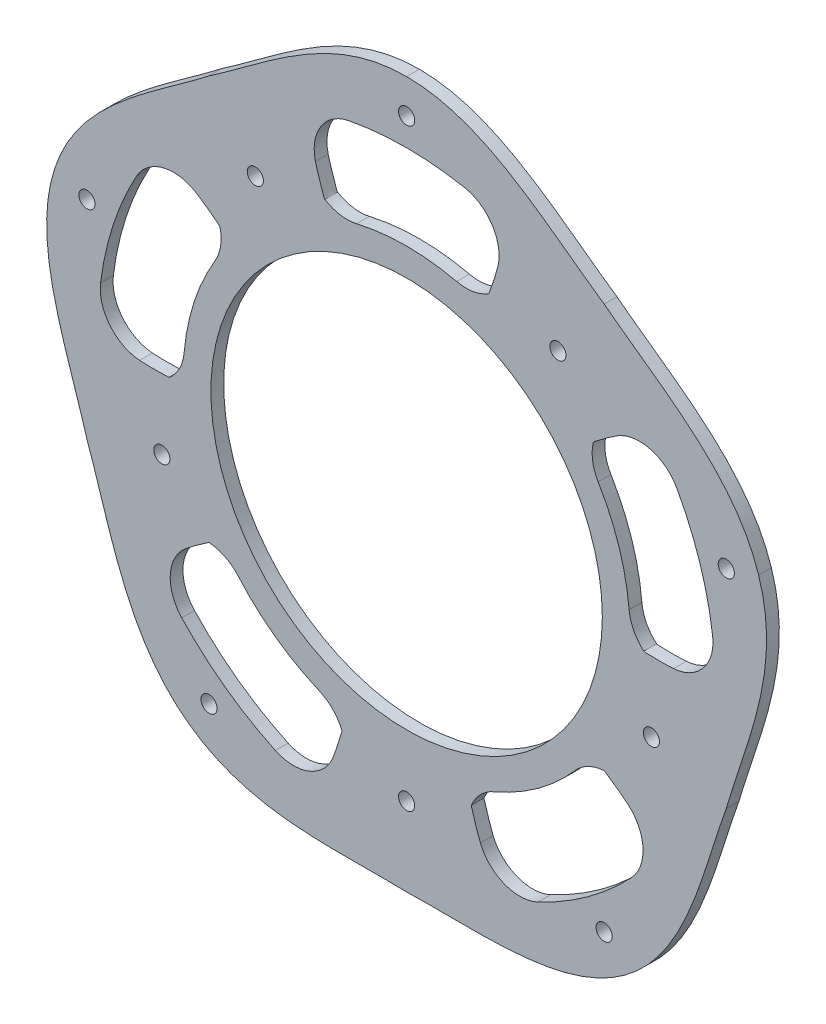
SolidWorks part; units mm, degrees
material "ABS"
ref_plane "Płaszczyzna przednia" through (0, 0, 0) normal (0, 0, 1) x (1, 0, 0)
ref_plane "Płaszczyzna górna" through (0, 0, 0) normal (0, 1, 0) x (1, 0, 0)
ref_plane "Płaszczyzna prawa" through (0, 0, 0) normal (1, 0, 0) x (0, 0, -1)
sketch "Szkic1" plane through (0, 0, 0) normal (0, 0, 1) x (1, 0, 0)
  line L0 (0, 0) -> (51.1373, 70.3845) construction
  line L1 (0, 0) -> (0, 87) construction
  circle A0 centre (0, 0) radius 79 construction
  circle A5 centre (0, 79) radius 1.9
  circle A9 centre (75.1335, 24.4123) radius 1.9
  circle A10 centre (46.435, -63.9123) radius 1.9
  circle A11 centre (-46.435, -63.9123) radius 1.9
  circle A12 centre (-75.1335, 24.4123) radius 1.9
  circle A13 centre (0, 0) radius 87 construction
  circle A54 centre (0, 0) radius 72.5
  circle A55 centre (0, 0) radius 46
  circle A56 centre (0, 0) radius 52
  circle A57 centre (0, 0) radius 68.5
  circle A59 centre (35.561, 48.9455) radius 1.9
  circle A60 centre (0, 0) radius 60.5 construction
  circle A64 centre (57.5389, -18.6955) radius 1.9
  circle A65 centre (0, -60.5) radius 1.9
  circle A66 centre (-57.5389, -18.6955) radius 1.9
  circle A67 centre (-35.561, 48.9455) radius 1.9
  spline S0 degree 3 poles (0, 87) (18.2248, 86.9986) (32.2889, 73.5369) (46.435, 63.9123) knots 0 0 0 0 1 1 1 1
  spline S1 degree 3 poles (82.7419, 26.8845) (77.1088, 44.2169) (59.9599, 53.4327) (46.435, 63.9123) knots 0 0 0 0 1 1 1 1
  spline S2 degree 3 poles (82.7419, 26.8845) (88.3724, 9.5512) (79.9156, -7.9844) (75.1335, -24.4123) knots 0 0 0 0 1 1 1 1
  spline S3 degree 3 poles (51.1373, -70.3845) (65.8807, -59.6711) (69.3462, -40.5137) (75.1335, -24.4123) knots 0 0 0 0 1 1 1 1
  spline S4 degree 3 poles (51.1373, -70.3845) (36.3923, -81.0957) (17.1016, -78.4715) (0, -79) knots 0 0 0 0 1 1 1 1
  spline S5 degree 3 poles (-51.1373, -70.3845) (-36.3923, -81.0957) (-17.1016, -78.4715) (0, -79) knots 0 0 0 0 1 1 1 1
  spline S6 degree 3 poles (-51.1373, -70.3845) (-65.8807, -59.6711) (-69.3462, -40.5137) (-75.1335, -24.4123) knots 0 0 0 0 1 1 1 1
  spline S7 degree 3 poles (-82.7419, 26.8845) (-88.3724, 9.5512) (-79.9156, -7.9844) (-75.1335, -24.4123) knots 0 0 0 0 1 1 1 1
  spline S8 degree 3 poles (-82.7419, 26.8845) (-77.1088, 44.2169) (-59.9599, 53.4327) (-46.435, 63.9123) knots 0 0 0 0 1 1 1 1
  spline S9 degree 3 poles (0, 87) (-18.2248, 86.9986) (-32.2889, 73.5369) (-46.435, 63.9123) knots 0 0 0 0 1 1 1 1
  point P18 (0, 0)
  point P27 (0, 0)
  point P64 (0, 0)
  point P69 (0, 0)
  point P188 (0, 0)
  dimension "D1" = 158
  dimension "D2" = 145
  dimension "D3" = 92
  dimension "D4" = 3.8
  dimension "D5" = 6
  dimension "D8" = 174
  dimension "D10" = 121
  dimension "D11" = 3.8
  dimension "D9" = 36
  dimension "D12" = 5
  dimension "D6" = 4
  dimension "D7" = 5
extrude "Dodanie-wyciągnięcie1" add sketch "Szkic1" along normal blind 3 contours S0 S9 S8 S7 S6 S5 S4 S3 S2 S1 A5 A54 A9 A10 A11 A12 | A56 A55 | A57 A56 | A54 A57 region at (-70.4494, 0, 0) region at (-50.5292, 0, 0) region at (-66.5625, 0, 0) region at (23.5794, 77.0008, 0)
sketch "Szkic2" plane through (0, 0, 3) normal (0, 0, 1) x (1, 0, 0)
  line L0 (0, 0) -> (0, 79) construction
  arc A0 (10.6305, 51.4125) -> (-11.76, 51.1659) centre (0, 0) ccw
  arc A6 (19.2098, 52.3761) -> (11.76, 51.1659) centre (14, 60.9118) cw
  arc A7 (21.4378, 59.0017) -> (13.6035, 71.2123) centre (11.7271, 61.3899) ccw
  arc A8 (-10.6305, 51.4125) -> (11.76, 51.1659) centre (0, 0) cw
  circle A9 centre (0, 0) radius 72.5
  arc A10 (-21.4378, 59.0017) -> (-13.6035, 71.2123) centre (-11.7271, 61.3899) cw
  arc A11 (-19.2098, 52.3761) -> (-11.76, 51.1659) centre (-14, 60.9118) ccw
  spline S0 degree 3 poles (-19.2098, 52.3761) (-19.3839, 52.4824) (-20.4272, 55.3893) (-21.2421, 58.2059) (-21.4378, 59.0017) knots 0.234742 0.234742 0.234742 0.234742 0.256094 0.345793 0.345793 0.345793 0.345793
  spline S1 degree 3 poles (19.2098, 52.3761) (19.3839, 52.4824) (20.4272, 55.3893) (21.2421, 58.2059) (21.4378, 59.0017) knots 0.234742 0.234742 0.234742 0.234742 0.256094 0.345793 0.345793 0.345793 0.345793
  dimension "D1" = 105
  dimension "D3" = 23.4543
  dimension "D4" = 28
extrude "Wytnij-wyciągnięcie1" cut sketch "Szkic2" against normal blind 10 contours A0 L0 S0 | L0 A0 region at (0, 61.5803, 3)
pattern_circular "Szyk kołowy1" count 5 over 360 about axis through (0, 0, 0) along (0, 0, 1) of "Wytnij-wyciągnięcie1"
